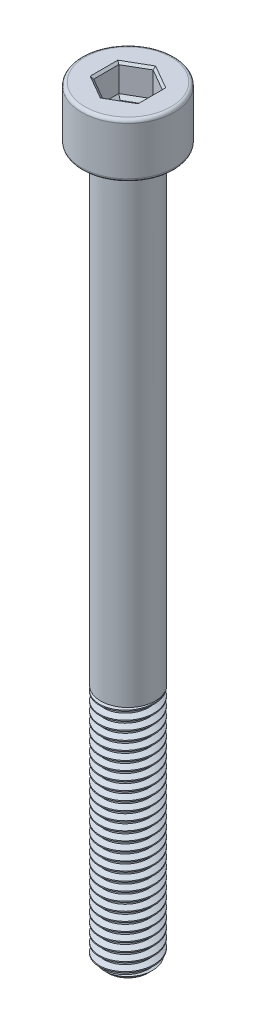
SolidWorks part; units mm, degrees
material "AISI Type A2 Tool Steel"
ref_plane "Front Plane" through (0, 0, 0) normal (0, 0, 1) x (1, 0, 0)
ref_plane "Top Plane" through (0, 0, 0) normal (0, 1, 0) x (1, 0, 0)
ref_plane "Right Plane" through (0, 0, 0) normal (1, 0, 0) x (0, 0, -1)
sketch "Sketch1" plane through (0, 0, 0) normal (0, 1, 0) x (1, 0, 0)
  circle A0 centre (0, 0) radius 2.5
  dimension "D1" = 5
extrude "Boss-Extrude1" add sketch "Sketch1" along normal blind 22
thread "Thread1" pitch 0.8 start angle 0, offset 1, length 0, pitch 0.8, diameter 5
ref_plane "Plane1" through (-2.5, 23, 0) normal (0, 0, 1) x (-1, 0, 0)
sketch "Thread Profile1" plane through (-2.5, 23, 0) normal (0, 0, 1) x (-1, 0, 0)
  line L0 (0, 0) -> (0, 0.8) construction
  line L11 (0, 0) -> (0, 0.7)
  line L12 (0, 0.7) -> (-0.433, 0.45)
  line L13 (-0.433, 0.45) -> (-0.433, 0.25)
  line L15 (-0.433, 0.25) -> (0, 0)
  line L17 (-0.433, 0.35) -> (0, 0.35) construction
  point P2 (0, 0)
  dimension "Pitch" = 0.8
  dimension "Profile_Angle" = 60
  dimension "Profile_Land" = 0.2
  dimension "Profile_Height" = 0.433
sketch "Sketch2" plane through (0, 22, 0) normal (0, 1, 0) x (1, 0, 0)
  circle A0 centre (0, 0) radius 2.5
  dimension "D1" = 5
extrude "Boss-Extrude2" add sketch "Sketch2" along normal blind 43
sketch "Sketch3" plane through (0, 65, 0) normal (0, 1, 0) x (1, 0, 0)
  circle A0 centre (0, 0) radius 4.25
  dimension "D1" = 8.5
extrude "Boss-Extrude3" add sketch "Sketch3" along normal blind 5
fillet "Fillet1" radius 0.3 2 edges at (0, 65, 4.25) (0, 70, 4.25)
sketch "Sketch4" plane through (0, 0, 0) normal (0, 0, 1) x (1, 0, 0)
  line L0 (0, 0) -> (0, 0.4416) construction
  line L1 (0, 0) -> (2.51, 0) construction
  line L2 (2.51, 0) -> (2.51, 0.7)
  line L3 (2.51, 0.7) -> (1.81, 0)
  line L4 (1.81, 0) -> (2.51, 0)
  dimension "D1" = 0.7
  dimension "D2" = 45
  dimension "D3" = 2.51
revolve "Cut-Revolve1" cut sketch "Sketch4" angle 360 about L0
sketch "Sketch5" plane through (0, 70, 0) normal (0, 1, 0) x (1, 0, 0)
  line L1 (0, 2.3094) -> (-2, 1.1547)
  line L2 (-2, 1.1547) -> (-2, -1.1547)
  line L3 (-2, -1.1547) -> (0, -2.3094)
  line L4 (0, -2.3094) -> (2, -1.1547)
  line L5 (2, -1.1547) -> (2, 1.1547)
  line L6 (2, 1.1547) -> (0, 2.3094)
  circle A0 centre (0, 0) radius 2 construction
  dimension "D1" = 4
extrude "Cut-Extrude1" cut sketch "Sketch5" against normal blind 2.5
chamfer "Chamfer1" distance 0.2 angle 45 6 edges at (-1, 70, 1.7321) (1, 70, 1.7321) (2, 70, 0) (1, 70, -1.7321) (-1, 70, -1.7321) (-2, 70, 0)
sketch "Sketch6" plane through (0, 67.5, 0) normal (0, 1, 0) x (1, 0, 0)
  line L1 (0, 2.3094) -> (-2, 1.1547)
  line L2 (-2, 1.1547) -> (-2, -1.1547)
  line L3 (-2, -1.1547) -> (0, -2.3094)
  line L4 (0, -2.3094) -> (2, -1.1547)
  line L5 (2, -1.1547) -> (2, 1.1547)
  line L6 (2, 1.1547) -> (0, 2.3094)
  circle A0 centre (0, 0) radius 2 construction
extrude "Cut-Extrude2" cut sketch "Sketch6" against normal blind 0.3 draft 45
